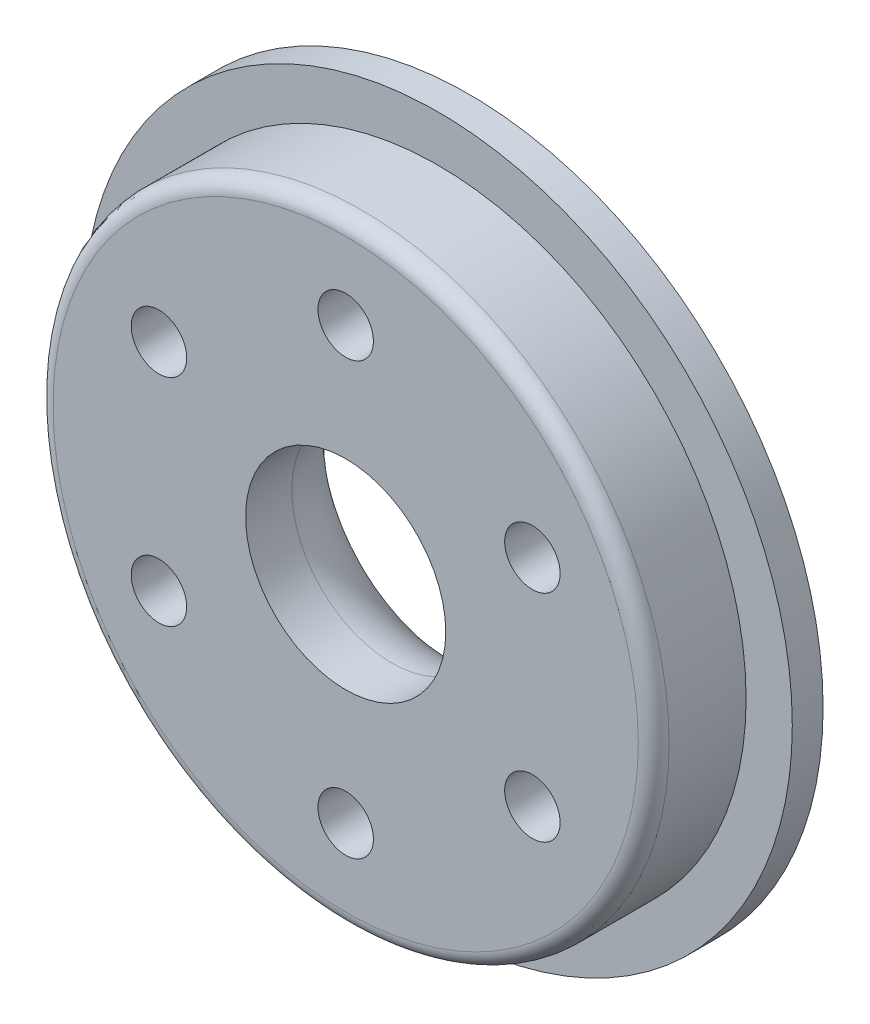
SolidWorks part; units mm, degrees
ref_plane "前视基准面" through (0, 0, 0) normal (0, 0, 1) x (1, 0, 0)
ref_plane "上视基准面" through (0, 0, 0) normal (0, 1, 0) x (1, 0, 0)
ref_plane "右视基准面" through (0, 0, 0) normal (1, 0, 0) x (0, 0, -1)
other "Configuration Table"
sketch "草图1" plane through (0, 0, 0) normal (0, 0, 1) x (1, 0, 0)
  circle A0 centre (0, 0) radius 23
  dimension "D1" = 46
extrude "凸台-拉伸1" add sketch "草图1" along normal blind 2
sketch "草图2" plane through (0, 0, 2) normal (0, 0, 1) x (1, 0, 0)
  circle A0 centre (0, 0) radius 20
  dimension "D1" = 40
extrude "凸台-拉伸2" add sketch "草图2" along normal blind 6
sketch "草图3" plane through (0, 0, 8) normal (0, 0, 1) x (1, 0, 0)
  circle A0 centre (0, 0) radius 14 construction
  circle A1 centre (0, 14) radius 1.8
  circle A2 centre (12.1244, 7) radius 1.8
  circle A3 centre (12.1244, -7) radius 1.8
  circle A4 centre (0, -14) radius 1.8
  circle A5 centre (-12.1244, -7) radius 1.8
  circle A6 centre (-12.1244, 7) radius 1.8
  point P17 (0, 0)
  dimension "D1" = 28
  dimension "D2" = 3.6
  dimension "D3" = 6
extrude "切除-拉伸1" cut sketch "草图3" against normal through all
sketch "草图4" plane through (0, 0, 8) normal (0, 0, 1) x (1, 0, 0)
  circle A0 centre (0, 0) radius 10
  dimension "D1" = 20
extrude "切除-拉伸2" cut sketch "草图4" against normal through all
fillet "圆角1" radius 1 1 edges at (20, 0, 8)
sketch "草图8" plane through (0, 0, 0) normal (0, 0, -1) x (-1, 0, 0)
  line L0 (-10.5078, 9.8) -> (-13.7409, 4.2) construction
  line L1 (-10.5078, 9.8) -> (-13.7409, 9.8)
  line L2 (-13.7409, 9.8) -> (-15.3575, 7)
  line L3 (-15.3575, 7) -> (-13.7409, 4.2)
  line L4 (-13.7409, 4.2) -> (-10.5078, 4.2)
  line L5 (-10.5078, 4.2) -> (-8.8912, 7)
  line L6 (-8.8912, 7) -> (-10.5078, 9.8)
  line L7 (3.2332, 14) -> (1.6166, 16.8)
  line L8 (1.6166, 16.8) -> (-1.6166, 16.8)
  line L9 (-1.6166, 16.8) -> (-3.2332, 14)
  line L10 (-3.2332, 14) -> (-1.6166, 11.2)
  line L11 (-1.6166, 11.2) -> (1.6166, 11.2)
  line L12 (1.6166, 11.2) -> (3.2332, 14)
  line L13 (3.2332, 14) -> (-3.2332, 14) construction
  line L14 (13.7409, 4.2) -> (15.3575, 7)
  line L15 (15.3575, 7) -> (13.7409, 9.8)
  line L16 (13.7409, 9.8) -> (10.5078, 9.8)
  line L17 (10.5078, 9.8) -> (8.8912, 7)
  line L18 (8.8912, 7) -> (10.5078, 4.2)
  line L19 (10.5078, 4.2) -> (13.7409, 4.2)
  line L20 (13.7409, 4.2) -> (10.5078, 9.8) construction
  line L21 (10.5078, -9.8) -> (13.7409, -9.8)
  line L22 (13.7409, -9.8) -> (15.3575, -7)
  line L23 (15.3575, -7) -> (13.7409, -4.2)
  line L24 (13.7409, -4.2) -> (10.5078, -4.2)
  line L25 (10.5078, -4.2) -> (8.8912, -7)
  line L26 (8.8912, -7) -> (10.5078, -9.8)
  line L27 (10.5078, -9.8) -> (13.7409, -4.2) construction
  line L28 (-3.2332, -14) -> (-1.6166, -16.8)
  line L29 (-1.6166, -16.8) -> (1.6166, -16.8)
  line L30 (1.6166, -16.8) -> (3.2332, -14)
  line L31 (3.2332, -14) -> (1.6166, -11.2)
  line L32 (1.6166, -11.2) -> (-1.6166, -11.2)
  line L33 (-1.6166, -11.2) -> (-3.2332, -14)
  line L34 (-3.2332, -14) -> (3.2332, -14) construction
  line L35 (-13.7409, -4.2) -> (-15.3575, -7)
  line L36 (-15.3575, -7) -> (-13.7409, -9.8)
  line L37 (-13.7409, -9.8) -> (-10.5078, -9.8)
  line L38 (-10.5078, -9.8) -> (-8.8912, -7)
  line L39 (-8.8912, -7) -> (-10.5078, -4.2)
  line L40 (-10.5078, -4.2) -> (-13.7409, -4.2)
  line L41 (-13.7409, -4.2) -> (-10.5078, -9.8) construction
  circle A0 centre (0, 0) radius 14 construction
  circle A1 centre (-12.1244, 7) radius 2.8 construction
  circle A2 centre (0, 14) radius 2.8 construction
  circle A3 centre (12.1244, 7) radius 2.8 construction
  circle A4 centre (12.1244, -7) radius 2.8 construction
  circle A5 centre (0, -14) radius 2.8 construction
  circle A6 centre (-12.1244, -7) radius 2.8 construction
  point P54 (0, 0)
  dimension "D1" = 5.6
  dimension "D2" = 6
extrude "切除-拉伸5" cut sketch "草图8" against normal blind 2.8
sketch "草图9" plane through (0, 0, 0) normal (0, 0, -1) x (-1, 0, 0)
  circle A0 centre (0, 0) radius 10
  circle A1 centre (0, 0) radius 6.5
  dimension "D1" = 13
extrude "凸台-拉伸3" add sketch "草图9" against normal blind 11
sketch "草图10" plane through (0, 0, 11) normal (0, 0, 1) x (1, 0, 0)
  circle A0 centre (0, 0) radius 8.5
  circle A1 centre (0, 0) radius 10
  circle A2 centre (0, 0) radius 10
  dimension "D2" = 17
  dimension "D1" = 0
extrude "切除-拉伸6" cut sketch "草图10" against normal blind 3
fillet "圆角3" radius 1.5 1 edges at (8.5, 0, 11)
fillet "圆角4" radius 5 1 edges at (-6.5, 0, 0)
sketch "草图11" plane through (0, 0, 8) normal (0, 0, 1) x (1, 0, 0)
  circle A0 centre (0, 0) radius 8.5
extrude "切除-拉伸7" cut sketch "草图11" along normal through all
